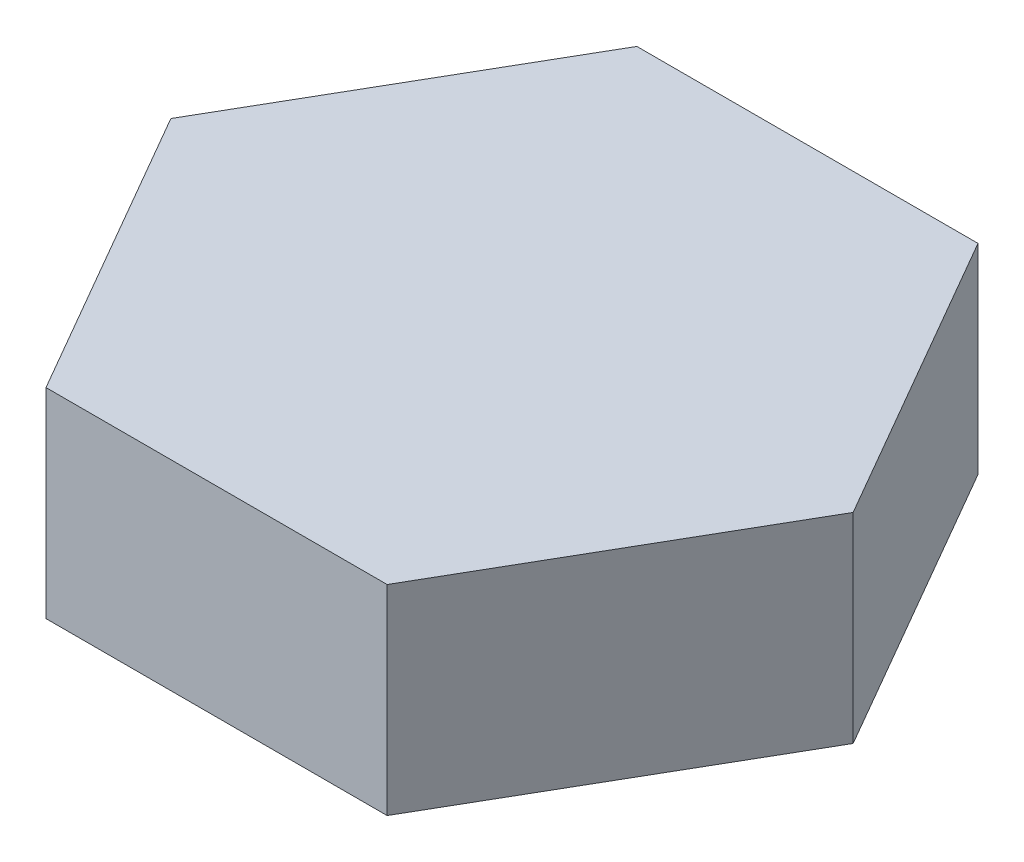
SolidWorks part; units mm, degrees
ref_plane "Front Plane" through (0, 0, 0) normal (0, 0, 1) x (1, 0, 0)
ref_plane "Top Plane" through (0, 0, 0) normal (0, 1, 0) x (1, 0, 0)
ref_plane "Right Plane" through (0, 0, 0) normal (1, 0, 0) x (0, 0, -1)
sketch "Sketch1" plane through (0, 0, 0) normal (0, 1, 0) x (1, 0, 0)
  line L1 (3.4641, 6) -> (-3.4641, 6)
  line L2 (-3.4641, 6) -> (-6.9282, 0)
  line L3 (-6.9282, 0) -> (-3.4641, -6)
  line L4 (-3.4641, -6) -> (3.4641, -6)
  line L5 (3.4641, -6) -> (6.9282, 0)
  line L6 (6.9282, 0) -> (3.4641, 6)
  circle A0 centre (0, 0) radius 6 construction
  point P1 (0, 0)
  point P10 (3.4557, 6.0048)
  dimension "D1" = 12
extrude "Boss-Extrude1" add sketch "Sketch1" along normal blind 4.064
sketch "Sketch2" plane through (0, 4.064, 0) normal (0, 1, 0) x (1, 0, 0)
  circle A0 centre (0, 0) radius 4.2496
